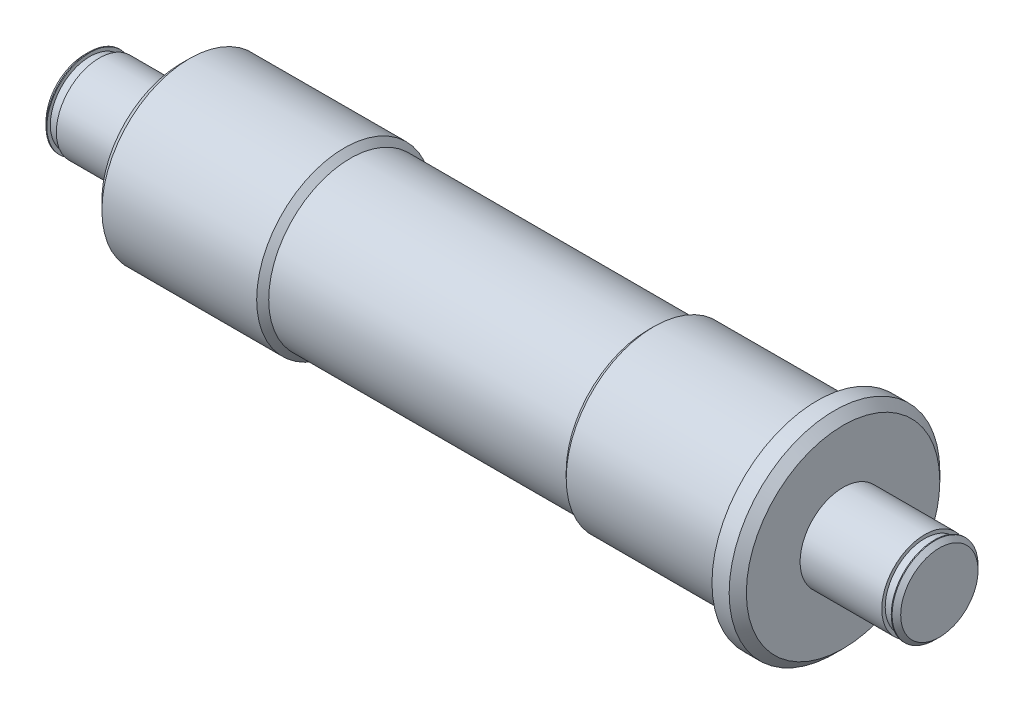
SolidWorks part; units mm, degrees
ref_plane "Płaszczyzna przednia" through (0, 0, 0) normal (0, 0, 1) x (1, 0, 0)
ref_plane "Płaszczyzna górna" through (0, 0, 0) normal (0, 1, 0) x (1, 0, 0)
ref_plane "Płaszczyzna prawa" through (0, 0, 0) normal (1, 0, 0) x (0, 0, -1)
sketch "Szkic1" plane through (0, 0, 0) normal (0, 0, 1) x (1, 0, 0)
  line L0 (0, 0) -> (0, 5)
  line L7 (11.2, 10.2) -> (31.2, 10.2)
  line L8 (31.2, 10.2) -> (31.2, 9.5)
  line L9 (31.2, 9.5) -> (65.2, 9.5)
  line L10 (65.2, 9.5) -> (65.2, 10.2)
  line L11 (65.2, 10.2) -> (85.2, 10.2)
  line L12 (85.2, 10.2) -> (85.2, 12.25)
  line L13 (85.2, 12.25) -> (88.2, 12.25)
  line L14 (88.2, 12.25) -> (88.2, 5)
  line L15 (88.2, 5) -> (97.7, 5)
  line L16 (99.4, 5) -> (99.4, 0)
  line L23 (99.4, 0) -> (0, 0)
  line L24 (-10.6747, 0) -> (-4.106, 0) construction
  line L25 (0, 5) -> (0.6, 5)
  line L26 (0.6, 5) -> (0.6, 4.6)
  line L27 (0.6, 4.6) -> (1.7, 4.6)
  line L28 (1.7, 4.6) -> (1.7, 5)
  line L29 (1.7, 5) -> (11.2, 5)
  line L30 (11.2, 5) -> (11.2, 10.2)
  line L33 (97.7, 5) -> (97.7, 4.6)
  line L34 (97.7, 4.6) -> (98.8, 4.6)
  line L35 (98.8, 4.6) -> (98.8, 5)
  line L36 (98.8, 5) -> (99.4, 5)
  dimension "D1" = 10
  dimension "D2" = 20.4
  dimension "D3" = 9.5
  dimension "D4" = 9.5
  dimension "D5" = 10
  dimension "D6" = 9.2
  dimension "D7" = 0.6
  dimension "D8" = 1.1
  dimension "D9" = 20
  dimension "D10" = 74
  dimension "D11" = 20
  dimension "D12" = 19
  dimension "D13" = 24.5
  dimension "D14" = 3
  dimension "D15" = 1.1
  dimension "D16" = 0.6
  dimension "D17" = 9.2
revolve "Obrót1" add sketch "Szkic1" angle 360 about L24
chamfer "Sfazowanie1" distance 1 angle 45 4 edges at (65.2, 0, 10.2) (31.2, 0, 10.2) (88.2, 0, 12.25) (11.2, 0, 10.2)
chamfer "Sfazowanie2" distance 0.5 angle 45 2 edges at (99.4, 0, 5) (0, 0, 5)
